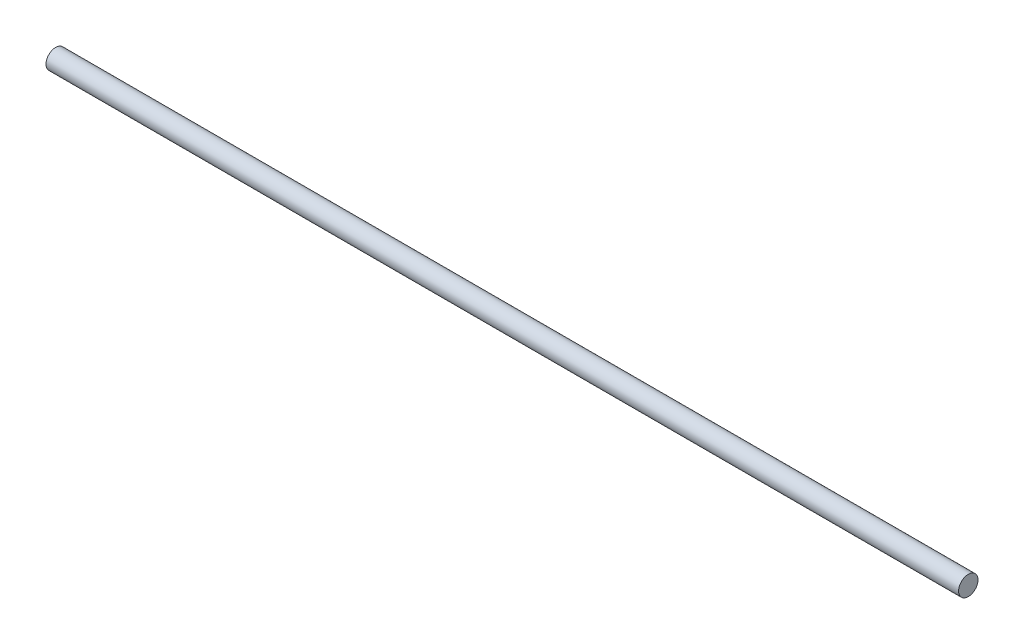
SolidWorks part; units mm, degrees
ref_plane "Front Plane" through (0, 0, 0) normal (0, 0, 1) x (1, 0, 0)
ref_plane "Top Plane" through (0, 0, 0) normal (0, 1, 0) x (1, 0, 0)
ref_plane "Right Plane" through (0, 0, 0) normal (1, 0, 0) x (0, 0, -1)
sketch "Sketch1" plane through (0, 0, 0) normal (1, 0, 0) x (0, 0, -1)
  circle A0 centre (0, 0) radius 3.175
  dimension "D1" = 6.35
extrude "Boss-Extrude1" add sketch "Sketch1" along normal blind 298.45
